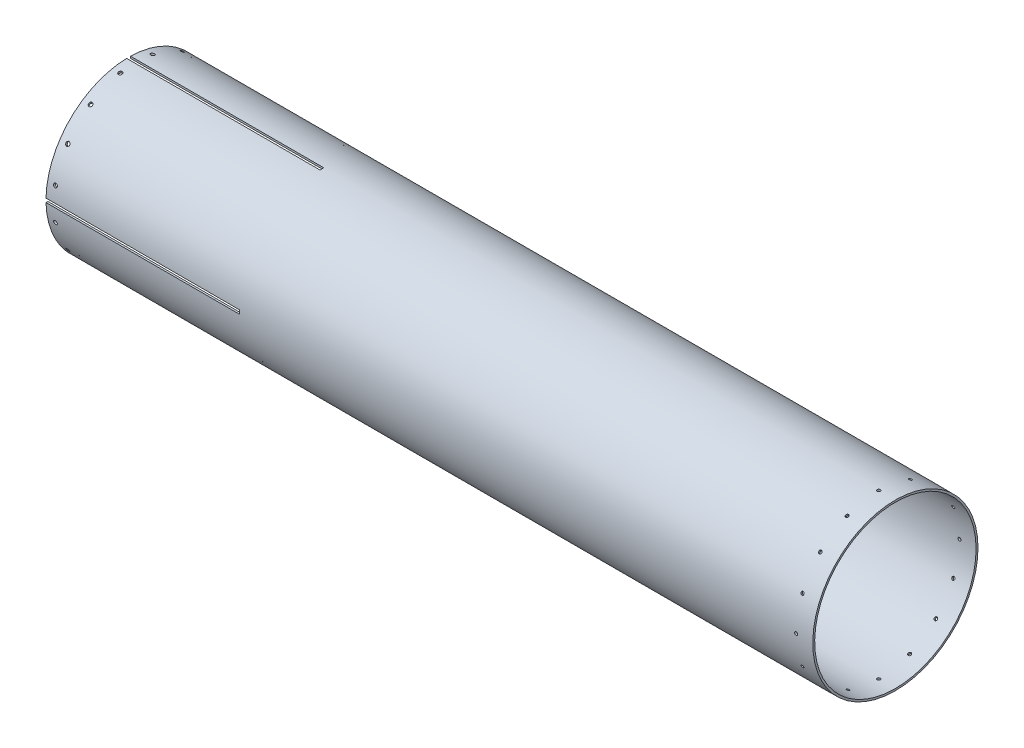
SolidWorks part; units mm, degrees
material "Thornel Mat VMA"
ref_plane "Płaszczyzna przednia" through (0, 0, 0) normal (0, 0, 1) x (1, 0, 0)
ref_plane "Płaszczyzna górna" through (0, 0, 0) normal (0, 1, 0) x (1, 0, 0)
ref_plane "Płaszczyzna prawa" through (0, 0, 0) normal (1, 0, 0) x (0, 0, -1)
sketch "Szkic1" plane through (0, 0, 0) normal (1, 0, 0) x (0, 0, -1)
  circle A0 centre (0, 0) radius 85
  circle A1 centre (0, 0) radius 87
  dimension "D1" = 170
  dimension "D2" = 174
extrude "Dodanie-wyciągnięcie1" add sketch "Szkic1" along normal blind 807.51
sketch "Szkic2" plane through (0, 0, 0) normal (1, 0, 0) x (0, 0, -1)
  line L0 (-129.3512, 0) -> (120.9381, 0) construction
  line L1 (0, 94.6472) -> (0, -98.8538) construction
  line L2 (-86.977, -2) -> (-2, -2)
  line L3 (-86.977, 2) -> (-2, 2)
  line L4 (-2, 86.977) -> (-2, 2)
  line L5 (2, 86.977) -> (2, 2)
  line L6 (-2, -2) -> (-2, -86.977)
  line L7 (2, 2) -> (86.977, 2)
  line L8 (-2, 94.6472) -> (-2, -98.8538) construction
  line L9 (2, -2) -> (86.977, -2)
  line L10 (-129.3512, 2) -> (120.9381, 2) construction
  line L11 (2, -2) -> (2, -86.977)
  line L12 (-129.3512, -2) -> (120.9381, -2) construction
  line L14 (2, 94.6472) -> (2, -98.8538) construction
  circle A0 centre (0, 0) radius 87 construction
  arc A1 (-86.977, 2) -> (-86.977, -2) centre (0, 0) ccw
  arc A2 (2, 86.977) -> (-2, 86.977) centre (0, 0) ccw
  arc A3 (86.977, -2) -> (86.977, 2) centre (0, 0) ccw
  arc A4 (-2, -86.977) -> (2, -86.977) centre (0, 0) ccw
  dimension "D1" = 2
  dimension "D2" = 2
  dimension "D3" = 2
  dimension "D4" = 2
extrude "Wytnij-wyciągnięcie1" cut sketch "Szkic2" along normal blind 203.6
sketch "Szkic3" plane through (0, 0, 0) normal (-1, 0, 0) x (0, 0, 1)
  line L0 (0, 100.995) -> (0, -98.9449) construction
  line L1 (0, 0) -> (16.9729, 85.3283) construction
  arc A0 (86.977, 2) -> (2, 86.977) centre (0, 0) ccw construction
  arc A1 (86.977, 2) -> (2, 86.977) centre (0, 0) ccw
  dimension "D1" = 11.25
sketch3d "Szkic 3D1" plane through (0, 0, 0) normal (0, 0, 1) x (1, 0, 0)
sketch3d "Szkic 3D2"
sketch "Szkic4" plane through (0, 85.3283, 16.9729) normal (0, 0.9808, 0.1951) x (1, 0, 0)
  line L0 (-15.3671, 0) -> (66.4096, 0) construction
  circle A0 centre (8.35, 0) radius 2
  dimension "D1" = 4
  dimension "D2" = 8.35
extrude "Wytnij-wyciągnięcie2" cut sketch "Szkic4" against normal blind 61.6
pattern_circular "Szyk kołowy1" count 16 over 360 about axis through (807.51, 0, 0) along (-1, 0, 0) of "Wytnij-wyciągnięcie2" reverse direction yes
sketch "Szkic5" plane through (807.51, 0, 0) normal (1, 0, 0) x (0, 0, -1)
  line L0 (0, 100.995) -> (0, -98.9449) construction
  line L1 (0, 87) -> (0, -98.9449)
  circle A0 centre (0, 0) radius 87 construction
  circle A1 centre (0, 0) radius 87
sketch3d "Szkic 3D3"
sketch "Szkic6" plane through (0, 87, 0) normal (0, 1, 0) x (1, 0, 0)
  line L0 (807.51, -87) -> (807.51, 87) construction
  line L1 (746.8047, 0) -> (827.5661, 0) construction
  circle A0 centre (790.01, 0) radius 1.6
  dimension "D1" = 3.2
  dimension "D2" = 17.5
extrude "Wytnij-wyciągnięcie3" cut sketch "Szkic6" against normal blind 61.6
pattern_circular "Szyk kołowy3" count 16 over 360 about axis through (807.51, 0, 0) along (-1, 0, 0) of "Wytnij-wyciągnięcie3"
